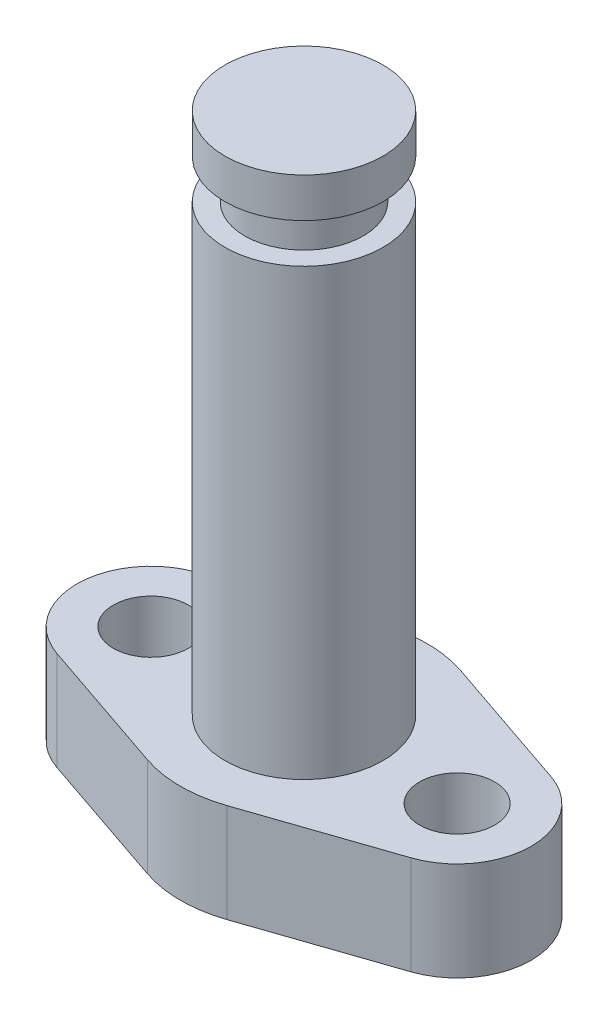
SolidWorks part; units mm, degrees
ref_plane "Front Plane" through (0, 0, 0) normal (0, 0, 1) x (1, 0, 0)
ref_plane "Top Plane" through (0, 0, 0) normal (0, 1, 0) x (1, 0, 0)
ref_plane "Right Plane" through (0, 0, 0) normal (1, 0, 0) x (0, 0, -1)
sketch "Sketch1" plane through (0, 0, 0) normal (0, 1, 0) x (1, 0, 0)
  line L0 (-8.9597, 3.5495) -> (-2.0161, 5.9159)
  line L1 (-8.9597, -3.5495) -> (-2.0161, -5.9159)
  line L2 (2.0161, 5.9159) -> (8.9597, 3.5495)
  line L3 (8.9597, -3.5495) -> (2.0161, -5.9159)
  circle A0 centre (0, 0) radius 4 construction
  circle A1 centre (0, 0) radius 6.25
  circle A2 centre (7.75, 0) radius 2.5 construction
  circle A3 centre (-7.75, 0) radius 2.5 construction
  circle A4 centre (-7.75, 0) radius 3.75
  circle A5 centre (7.75, 0) radius 3.75
  dimension "D1" = 7.5
  dimension "D2" = 8
  dimension "D3" = 12.5
  dimension "D4" = 5
extrude "Boss-Extrude1" add sketch "Sketch1" along normal blind 5 contours A1 A4 A3 | A1 A4 A3 | A5 A1 A4 | A4 L1 A1 | A5 A1 L3 | A1 A5 A2 | A5 A1 A2 | A5 L2 A1 | A4 A1 L0 region at (-8.4339, 0, 0) region at (-5.5796, 0, -4.1989) region at (0, 0, 0) region at (-5.5796, 0, 4.1989) region at (-5.1837, 0, 0) region at (5.5796, 0, -4.1989) region at (8.4339, 0, 0) region at (5.1837, 0, 0) region at (5.5796, 0, 4.1989)
sketch "Sketch2" plane through (0, 5, 0) normal (0, 1, 0) x (1, 0, 0)
  line L0 (0, -6.25) -> (0, 6.25) construction
  line L1 (11.5, 0) -> (-11.5, 0) construction
  arc A0 (-2.0161, -5.9159) -> (2.0161, -5.9159) centre (0, 0) ccw construction
  arc A1 (2.0161, 5.9159) -> (-2.0161, 5.9159) centre (0, 0) ccw construction
  arc A2 (8.9597, -3.5495) -> (8.9597, 3.5495) centre (7.75, 0) ccw construction
  arc A3 (-8.9597, 3.5495) -> (-8.9597, -3.5495) centre (-7.75, 0) ccw construction
  circle A4 centre (0, 0) radius 4
extrude "Boss-Extrude2" add sketch "Sketch2" along normal blind 22.5
sketch "Sketch3" plane through (0, 27.5, 0) normal (0, 1, 0) x (1, 0, 0)
  circle A0 centre (0, 0) radius 3
  dimension "D1" = 6
extrude "Boss-Extrude3" add sketch "Sketch3" along normal blind 2
sketch "Sketch4" plane through (0, 29.5, 0) normal (0, 1, 0) x (1, 0, 0)
  circle A0 centre (0, 0) radius 4
extrude "Boss-Extrude4" add sketch "Sketch4" along normal blind 2
hole_wizard "#6 Clearance Hole1" positions "Sketch5" profile "Sketch6" hole size "#6" standard "ANSI Inch" end condition through all
sketch "Sketch5" plane through (0, 5, 0) normal (0, 1, 0) x (1, 0, 0)
  point P0 (-7.75, 0)
  point P3 (7.75, 0)
sketch "Sketch6" plane through (-7.75, 5, 0) normal (1, 0, 0) x (0, 0, 1)
  line L0 (0, 0) -> (0, 5)
  line L1 (0, 5) -> (1.8986, 5)
  line L2 (1.8986, 5) -> (1.8986, 0)
  line L5 (1.8986, 0) -> (0, 0)
  line L11 (0, -6.35) -> (0, 107.95) construction
  dimension "Thru Hole Dia." = 3.7973
  dimension "Thru Hole Depth" = 5
